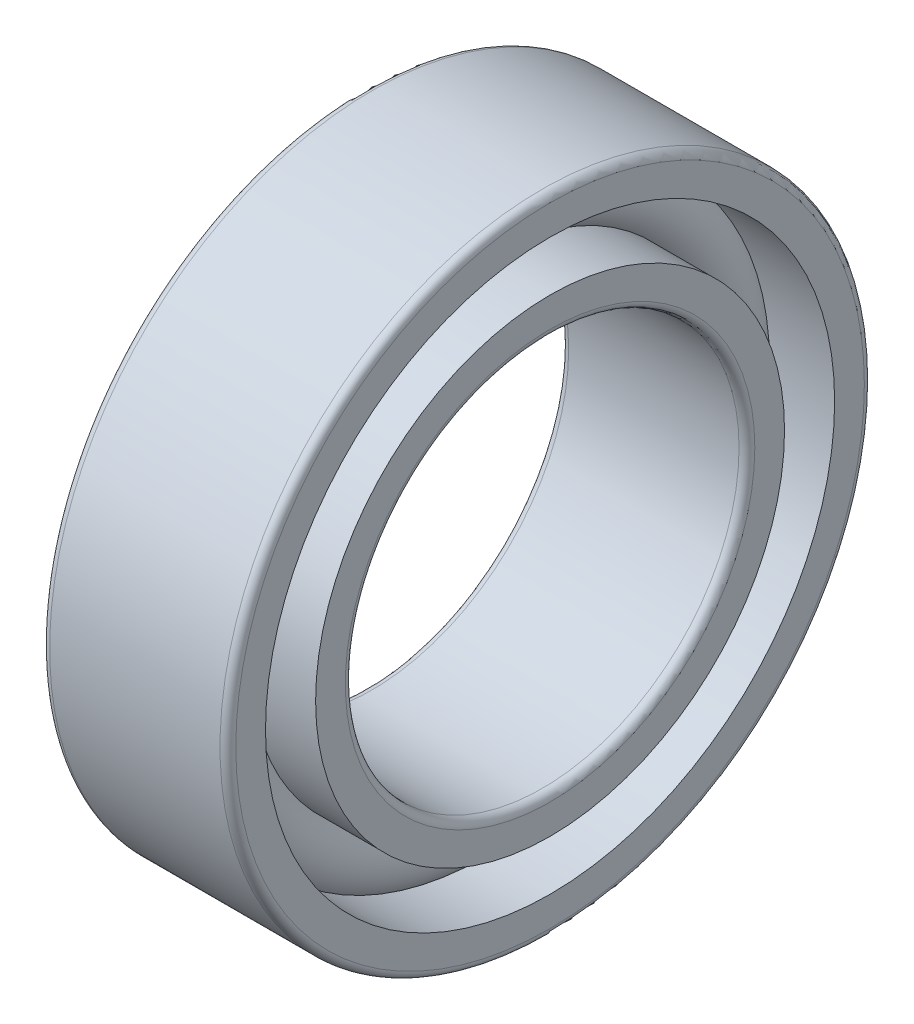
SolidWorks part; units mm, degrees
ref_plane "Plane1" through (0, 0, 0) normal (0, 0, 1) x (1, 0, 0)
ref_plane "Plane2" through (0, 0, 0) normal (0, 1, 0) x (1, 0, 0)
ref_plane "Plane3" through (0, 0, 0) normal (1, 0, 0) x (0, 0, -1)
sketch "Clipboard" plane through (0, 0, 0) normal (0, 0, 1) x (1, 0, 0)
  line L0 (-10, 0) -> (10, 0) construction
  line L1 (0, 0) -> (22.3471, -0.7804)
  line L2 (0, 0) -> (36.2279, 1.2651)
  line L3 (0, 0) -> (22.3471, -0.7804)
  line L4 (0, 0) -> (-22.3573, -0.3902)
  dimension "BallCLRad" = 36.25
sketch "CagSpiSke" plane through (0, 0, 0) normal (0, 0, 1) x (1, 0, 0)
  line L0 (0.525, 35.375) -> (0.525, 37.125)
  line L1 (0.525, 37.125) -> (-0.525, 37.125)
  line L2 (-0.525, 37.125) -> (-0.525, 35.375)
  line L3 (-0.525, 35.375) -> (0.525, 35.375)
  line L4 (-20.6375, 0) -> (20.6375, 0) construction
  line L5 (0, 0) -> (0, 23.7692) construction
  dimension "OD" = 74.25
  dimension "ID" = 70.75
revolve "CageSpine" add sketch "CagSpiSke" angle 0.001 about L4 reverse direction yes
ref_axis "Axis1" through (-50, 0, 0) along (1, 0, 0)
sketch "CagBalSke" plane through (0, 0, 0) normal (0, 0, 1) x (1, 0, 0)
  line L0 (-5.775, 36.25) -> (5.775, 36.25)
  line L1 (-1.905, 36.25) -> (1.905, 36.25) construction
  line L2 (-10, 0) -> (10, 0) construction
  line L3 (0, 0) -> (0, 24) construction
  arc A0 (5.775, 36.25) -> (-5.775, 36.25) centre (0, 36.25) cw
  dimension "BallCLRad" = 36.25
revolve "CageBall" [suppressed] add sketch "CagBalSke" angle 360 about L1 reverse direction yes
pattern_circular "CageBalls" [suppressed] count 2 every 180 about axis through (-50, 0, 0) along (1, 0, 0)
sketch "CagTrmODSke" plane through (0, 0, 0) normal (0, 0, 1) x (1, 0, 0)
  line L0 (5.776, 37.125) -> (5.776, 42.026)
  line L1 (5.776, 42.026) -> (-5.776, 42.026)
  line L2 (-5.776, 42.026) -> (-5.776, 37.125)
  line L3 (-5.776, 37.125) -> (5.776, 37.125)
  line L4 (-20.6375, 0) -> (20.6375, 0) construction
  line L5 (0, 0) -> (0, 25) construction
  dimension "Width" = 11.552
  dimension "ID" = 74.25
  dimension "OD" = 84.052
revolve "CageTrimOD" [suppressed] cut sketch "CagTrmODSke" angle 360 about L4 reverse direction yes
sketch "CagTrmIDSke" plane through (0, 0, 0) normal (0, 0, 1) x (1, 0, 0)
  line L0 (5.776, 30.476) -> (5.776, 35.375)
  line L1 (5.776, 35.375) -> (-5.776, 35.375)
  line L2 (-5.776, 35.375) -> (-5.776, 30.476)
  line L3 (-5.776, 30.476) -> (5.776, 30.476)
  line L4 (-20.6375, 0) -> (20.6375, 0) construction
  line L5 (0, 0) -> (0, 25) construction
  dimension "Width" = 11.552
  dimension "ID" = 60.952
  dimension "OD" = 70.75
revolve "CageTrimID" [suppressed] cut sketch "CagTrmIDSke" angle 360 about L4 reverse direction yes
sketch "BalSimSke" plane through (0, 0, 0) normal (0, 0, 1) x (1, 0, 0)
  line L0 (-10, 0) -> (10, 0) construction
  line L1 (-10, 36.25) -> (10, 36.25) construction
  line L2 (0, 0) -> (0, 23) construction
  circle A0 centre (0, 36.25) radius 5.25
  dimension "BallCLRad" = 36.25
  dimension "Ball_diameter" = 10.5
revolve "BallsSimplified" add sketch "BalSimSke" angle 360 about L0
sketch "BalDetSke" plane through (0, 0, 0) normal (0, 0, 1) x (1, 0, 0)
  line L0 (-5.25, 36.25) -> (5.25, 36.25)
  line L1 (-1.905, 36.25) -> (1.905, 36.25) construction
  line L2 (0, 0) -> (0, 25) construction
  arc A0 (5.25, 36.25) -> (-5.25, 36.25) centre (0, 36.25) cw
  dimension "BallCLRad" = 36.25
  dimension "Ball_diameter" = 10.5
revolve "BallDetailed" [suppressed] add sketch "BalDetSke" angle 360 about L1 reverse direction yes
sketch "InnRacSke" plane through (0, 0, 0) normal (0, 0, 1) x (1, 0, 0)
  line L0 (-3.8795, 32.75) -> (-13, 32.75)
  line L1 (-13, 32.75) -> (-13, 28.6)
  line L2 (-11.9, 27.5) -> (11.9, 27.5)
  line L3 (13, 28.6) -> (13, 32.75)
  line L4 (13, 32.75) -> (3.8795, 32.75)
  line L5 (-20.6375, 0) -> (20.6375, 0) construction
  line L6 (0, 0) -> (0, 30) construction
  arc A0 (-13, 28.6) -> (-11.9, 27.5) centre (-11.9, 28.6) ccw
  arc A1 (11.9, 27.5) -> (13, 28.6) centre (11.9, 28.6) ccw
  arc A2 (3.8795, 32.75) -> (-3.8795, 32.75) centre (0, 36.25) cw
  dimension "BallCLRad" = 36.25
  dimension "Fillet_radius" = 1.1
  dimension "Ball_diameter" = 10.45
  dimension "ID" = 55
  dimension "OD" = 65.5
  dimension "Width" = 26
revolve "InnerRace" add sketch "InnRacSke" angle 360 about L5 reverse direction yes
sketch "OutRacSke" plane through (0, 0, 0) normal (0, 0, 1) x (1, 0, 0)
  line L0 (-3.8795, 39.75) -> (-13, 39.75)
  line L1 (-13, 39.75) -> (-13, 43.9)
  line L2 (-11.9, 45) -> (11.9, 45)
  line L3 (13, 43.9) -> (13, 39.75)
  line L4 (13, 39.75) -> (3.8795, 39.75)
  line L5 (-20.6375, 0) -> (20.6375, 0) construction
  line L6 (0, 0) -> (0, 30) construction
  arc A0 (-13, 43.9) -> (-11.9, 45) centre (-11.9, 43.9) cw
  arc A1 (11.9, 45) -> (13, 43.9) centre (11.9, 43.9) cw
  arc A2 (3.8795, 39.75) -> (-3.8795, 39.75) centre (0, 36.25) ccw
  dimension "BallCLRad" = 36.25
  dimension "Fillet_radius" = 1.1
  dimension "Ball_diameter" = 10.45
  dimension "Width" = 26
revolve "OuterRace" add sketch "OutRacSke" angle 360 about L5 reverse direction yes
pattern_circular "BallsDetailed" [suppressed] count 2 every 180 about axis through (-50, 0, 0) along (1, 0, 0)
equation "\"BallCLRad@Clipboard\" = ( \"OD@OutRacSke\" + \"ID@InnRacSke\" ) / 4"
equation "\"BallCLRad@BalSimSke\" = \"BallCLRad@Clipboard\""
equation "\"BallCLRad@BalDetSke\" = \"BallCLRad@Clipboard\""
equation "\"BallCLRad@InnRacSke\" = \"BallCLRad@Clipboard\""
equation "\"BallCLRad@OutRacSke\" = \"BallCLRad@Clipboard\""
equation "\"Ball_diameter@InnRacSke\" = \"Ball_diameter@BalDetSke\" - 0.05"
equation "\"Ball_diameter@OutRacSke\" = \"Ball_diameter@BalDetSke\" - 0.05"
equation "\"Ball_diameter@BalSimSke\" = \"Ball_diameter@BalDetSke\""
equation "\"Width@OutRacSke\" = \"Width@InnRacSke\""
equation "\"Fillet_radius@OutRacSke\" = \"Fillet_radius@InnRacSke\""
equation "\"Max_count@Clipboard\" = int( 3.14159265 / atn(( \"Ball_diameter@BalDetSke\" / 2) / sqr( \"BallCLRad@Clipboard\"  *  \"BallCLRad@Clipboard\" - ( \"Ball_diameter@BalDetSke\" / 2) *  ( \"Ball_diameter@BalDetSke\" / 2))))"
equation "\"Max_count@Clipboard\" = ((sgn( \"Max_count@Clipboard\" - \"Count@Clipboard\" )-1)*( \"Max_count@Clipboard\" - \"Count@Clipboard\" ))/-2+ \"Count@Clipboard\""
equation "\"Count@BallsDetailed\" = int( \"Show_count@Clipboard\" ) "
equation "\"Count@BallsDetailed\" = ((sgn( \"Count@BallsDetailed\" - \"Max_count@Clipboard\" )-1)*( \"Count@BallsDetailed\" - \"Max_count@Clipboard\" ))/-2+ \"Max_count@Clipboard\""
equation "\"Count@BallsDetailed\" = ((sgn( \"Count@BallsDetailed\" - \"Min_count@Clipboard\" )+1)*( \"Count@BallsDetailed\" - \"Min_count@Clipboard\"))/2 +\"Min_count@Clipboard\""
equation "\"Angle@BallsDetailed\" = 360.0 / \"Max_count@Clipboard\""
equation "\"BallCLRad@CagBalSke\" = \"BallCLRad@Clipboard\""
equation "\"Count@CageBalls\" = \"Count@BallsDetailed\""
equation "\"Angle@CageBalls\" = \"Angle@BallsDetailed\""
equation "\"Angle@CageSpine\" =  \"Angle@CageBalls\" * ( \"Count@CageBalls\" -1 + int( \"Count@CageBalls\" / \"Max_count@Clipboard\" ) )  + 0.001 -  int( \"Count@CageBalls\" / \"Max_count@Clipboard\" ) * 0.001"
equation "\"Angle@CageSpine\" =  \"Angle@CageSpine\" * int( \"Min_count@Clipboard\" / 2) + int(1 / \"Min_count@Clipboard\")  * 0.001"
equation "\"CageWallOD@CagBalSke\" =  \"Ball_diameter@BalDetSke\" * 1.1"
equation "\"Thickness@CagSpiSke\" =  \"Ball_diameter@BalDetSke\" * 0.1"
equation "\"OD@CagTrmODSke\" = \"BallCLRad@Clipboard\" * 2 + \"CageWallOD@CagBalSke\" + 0.002"
equation "\"ID@CagTrmODSke\" = \"BallCLRad@Clipboard\" * 2 + \"Ball_diameter@BalDetSke\" / 6"
equation "\"OD@CagTrmIDSke\" = \"BallCLRad@Clipboard\" * 2 - \"Ball_diameter@BalDetSke\" / 6"
equation "\"ID@CagTrmIDSke\" = \"BallCLRad@Clipboard\" * 2 - \"CageWallOD@CagBalSke\" + 0.002"
equation "\"OD@CagSpiSke\" = \"ID@CagTrmODSke\""
equation "\"ID@CagSpiSke\" = \"OD@CagTrmIDSke\""
equation "\"Width@CagTrmODSke\" = \"CageWallOD@CagBalSke\" + 0.002"
equation "\"Width@CagTrmIDSke\" = \"CageWallOD@CagBalSke\" + 0.002"
